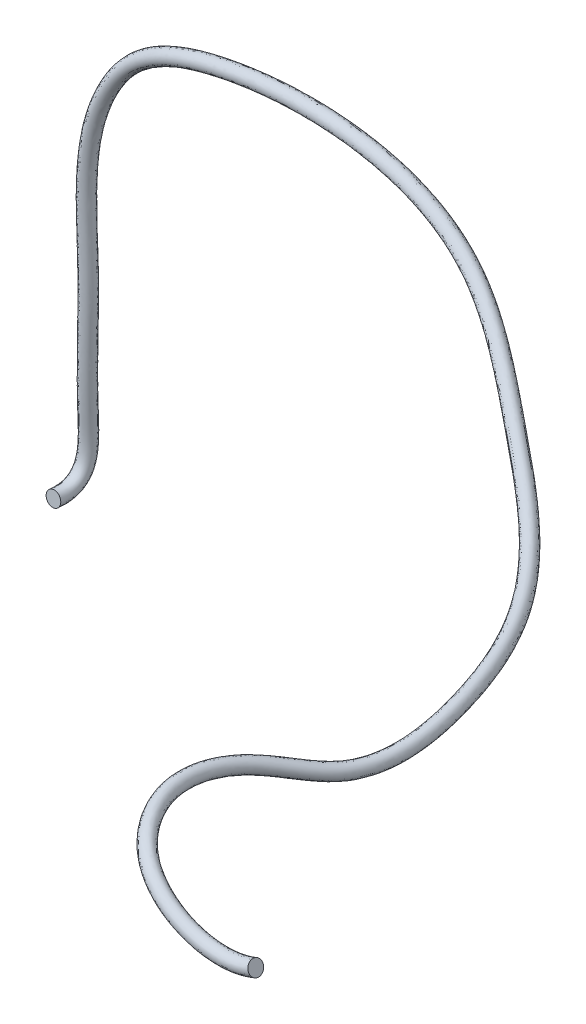
SolidWorks part; units mm, degrees
ref_plane "前视基准面" through (0, 0, 0) normal (0, 0, 1) x (1, 0, 0)
ref_plane "上视基准面" through (0, 0, 0) normal (0, 1, 0) x (1, 0, 0)
ref_plane "右视基准面" through (0, 0, 0) normal (1, 0, 0) x (0, 0, -1)
other "Configuration Table"
sketch3d "3D草图1"
  spline S0 degree 3 poles (350.5, -44.55, 26) (338.5697, -49.6138, 25.8266) (318.2853, -37.8135, 28.9578) (303.4529, -33.9894, 4.9093) (306.6524, -37.0758, -15.7102) (319.9184, -47.2118, -34.6634) (317.9225, -43.0858, -66.8472) (300.205, -43.5223, -103.5025) (262.6445, -39.4764, -133.1744) (222.4951, -38.0358, -165.524) (175.2475, -42.0721, -184.3677) (134.2948, -44.7016, -186.7642) (102.0076, -56.3931, -188.213) (88.3529, -83.64, -187.8782) (91.0396, -115.3902, -188.2741) (90.2728, -143.0104, -187.2407) (90.4206, -166.3191, -189.0324) (90.4, -165.2, -178.5) knots 0 0 0 0 0.071963 0.109633 0.149703 0.188592 0.253659 0.323371 0.42675 0.53129 0.628866 0.720863 0.775577 0.820583 0.889665 0.956704 1 1 1 1
sweep "扫描1" add path "3D草图1" circular profile diameter 4 parameters "D3"=4
